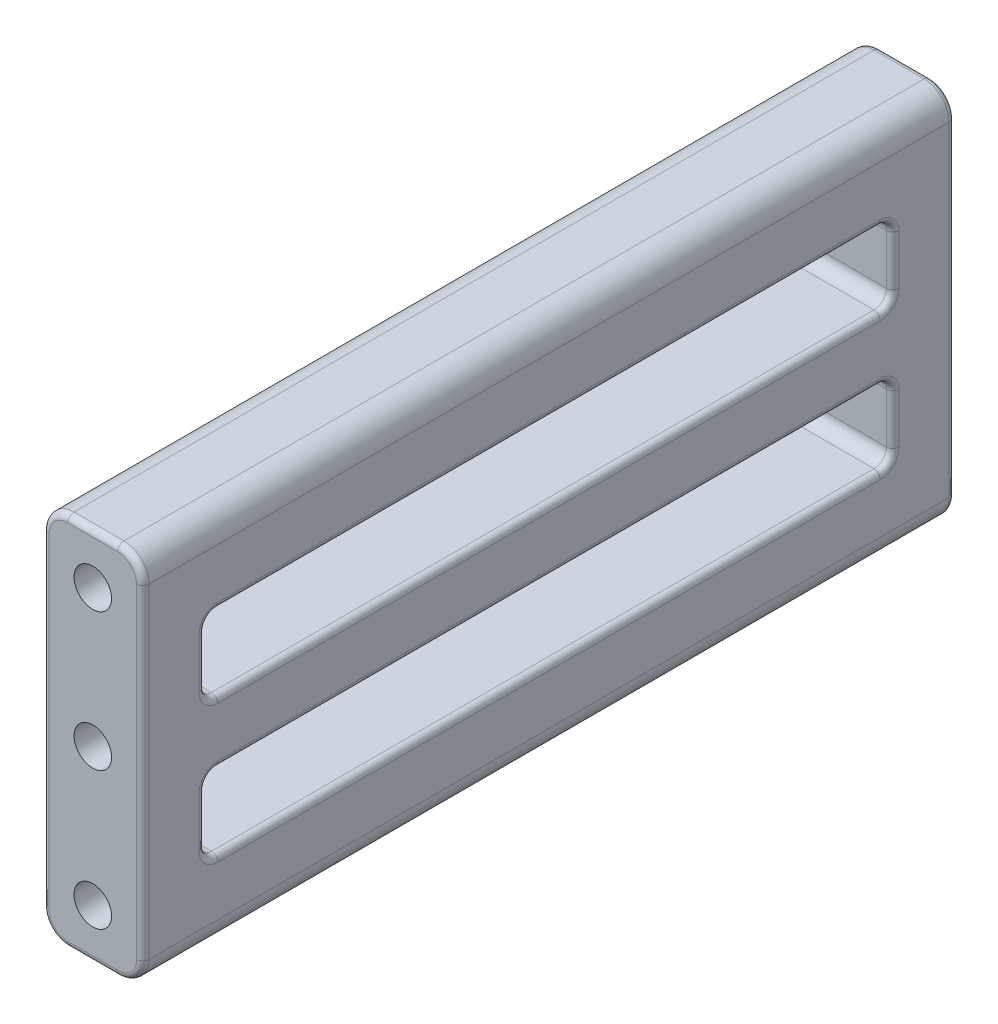
SolidWorks part; units mm, degrees
material "6061 Alloy"
ref_plane "Front Plane" through (0, 0, 0) normal (0, 0, 1) x (1, 0, 0)
ref_plane "Top Plane" through (0, 0, 0) normal (0, 1, 0) x (1, 0, 0)
ref_plane "Right Plane" through (0, 0, 0) normal (1, 0, 0) x (0, 0, -1)
sketch "Sketch1" plane through (0, 0, 0) normal (1, 0, 0) x (0, 0, -1)
  line L1 (-32.5, 15) -> (32.5, 15)
  line L2 (-32.5, 15) -> (-32.5, -15)
  line L3 (-32.5, -15) -> (32.5, -15)
  line L4 (32.5, 15) -> (32.5, -15)
  line L5 (-32.5, 15) -> (32.5, -15) construction
  line L6 (-32.5, -15) -> (32.5, 15) construction
  point P0 (0, 0)
  dimension "D1" = 65
  dimension "D2" = 30
extrude "Boss-Extrude1" add sketch "Sketch1" along normal blind 8
fillet "Fillet1" radius 2 4 edges at (8, -15, 0) (0, -15, 0) (0, 15, 0) (8, 15, 0)
fillet "Fillet2" radius 0.5 16 edges at (7.4142, 14.4142, -32.5) (4, 15, -32.5) (0.5858, 14.4142, -32.5) (0, 0, -32.5) (0.5858, -14.4142, -32.5) (4, -15, -32.5) (7.4142, -14.4142, -32.5) (8, 0, -32.5) (0.5858, -14.4142, 32.5) (0, 0, 32.5) (0.5858, 14.4142, 32.5) (4, 15, 32.5) (7.4142, 14.4142, 32.5) (8, 0, 32.5) (7.4142, -14.4142, 32.5) (4, -15, 32.5)
sketch "Sketch2" plane through (0, 0, -32.5) normal (0, 0, -1) x (-1, 0, 0)
  circle A0 centre (-4, 0) radius 1.5
  circle A1 centre (-4, 11) radius 1.5
  circle A2 centre (-4, -11) radius 1.5
  point P6 (0, 0)
  point P8 (0, 0)
  dimension "D2" = 3
  dimension "D3" = 11
  dimension "D4" = 11
  dimension "D1" = 4
extrude "Cut-Extrude1" cut sketch "Sketch2" against normal blind 10
sketch "Sketch3" plane through (8, 0, 0) normal (1, 0, 0) x (0, 0, -1)
  line L0 (-32.5, 0) -> (32.5, 0) construction
  line L1 (-27.5, 8.5) -> (27.5, 8.5)
  line L2 (-27.5, 8.5) -> (-27.5, 2.5)
  line L3 (-27.5, 2.5) -> (27.5, 2.5)
  line L4 (27.5, 8.5) -> (27.5, 2.5)
  line L9 (-32.5, -13) -> (-32.5, 13) construction
  line L10 (32.5, 13) -> (32.5, -13) construction
  line L12 (-27.5, -2.5) -> (27.5, -2.5)
  line L13 (27.5, -8.5) -> (27.5, -2.5)
  line L14 (-27.5, -8.5) -> (27.5, -8.5)
  line L15 (-27.5, -8.5) -> (-27.5, -2.5)
  line L16 (0, 15) -> (0, -15) construction
  line L17 (-32, 15) -> (32, 15) construction
  line L18 (32, -15) -> (-32, -15) construction
  dimension "D1" = 55
  dimension "D3" = 8.5
  dimension "D4" = 2.5
extrude "Cut-Extrude2" cut sketch "Sketch3" against normal blind 10
fillet "Fillet3" radius 1 8 edges at (4, -8.5, -27.5) (4, -2.5, -27.5) (4, -8.5, 27.5) (4, -2.5, 27.5) (4, 2.5, -27.5) (4, 8.5, -27.5) (4, 2.5, 27.5) (4, 8.5, 27.5)
fillet "Fillet4" radius 0.5 32 edges at (0, -8.2071, -27.2071) (0, -8.5, 0) (0, -8.2071, 27.2071) (0, -5.5, 27.5) (0, -2.7929, 27.2071) (0, -2.5, 0) (0, -2.7929, -27.2071) (0, -5.5, -27.5) (0, 2.7929, -27.2071) (0, 2.5, 0) (0, 2.7929, 27.2071) (0, 5.5, 27.5) (0, 8.2071, 27.2071) (0, 8.5, 0) (0, 8.2071, -27.2071) (0, 5.5, -27.5) (8, -8.2071, 27.2071) (8, -8.5, 0) (8, -8.2071, -27.2071) (8, -5.5, -27.5) (8, -2.7929, -27.2071) (8, -2.5, 0) (8, -2.7929, 27.2071) (8, -5.5, 27.5) (8, 2.7929, 27.2071) (8, 2.5, 0) (8, 2.7929, -27.2071) (8, 5.5, -27.5) (8, 8.2071, -27.2071) (8, 8.5, 0) (8, 8.2071, 27.2071) (8, 5.5, 27.5)
mirror "Mirror1" about plane through (0, 0, 0) normal (0, 0, 1) of "Cut-Extrude1"
